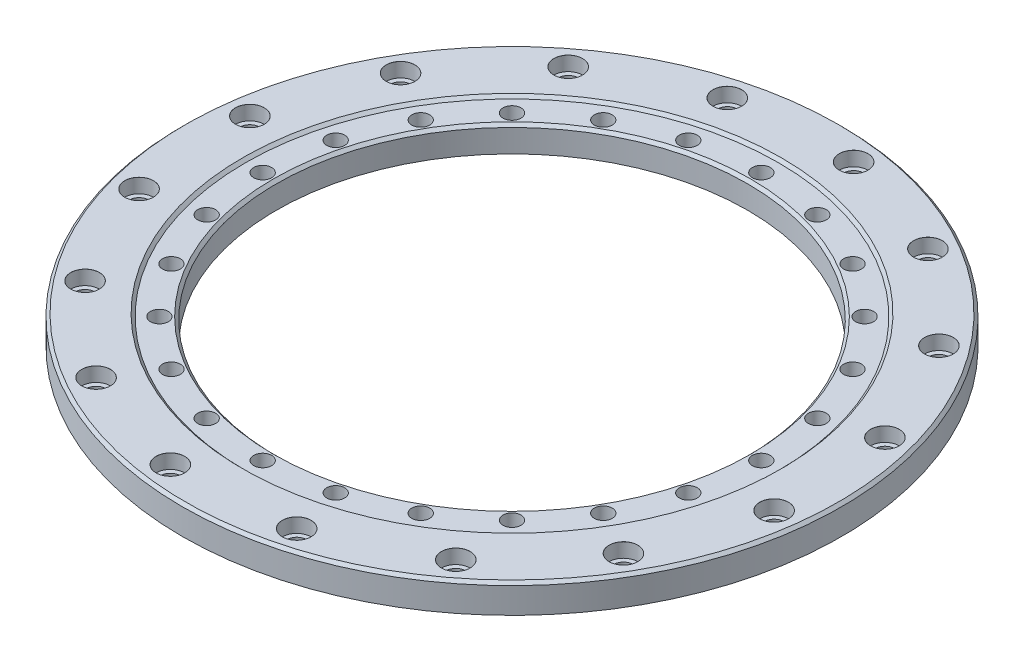
SolidWorks part; units mm, degrees
material "1.1191 (C45E)"
ref_plane "Front Plane" through (0, 0, 0) normal (0, 0, 1) x (1, 0, 0)
ref_plane "Top Plane" through (0, 0, 0) normal (0, 1, 0) x (1, 0, 0)
ref_plane "Right Plane" through (0, 0, 0) normal (1, 0, 0) x (0, 0, -1)
sketch "Sketch1" plane through (0, 0, 0) normal (1, 0, 0) x (0, 0, -1)
  line L0 (0, 0) -> (0, 173.9496) construction
  line L1 (-164.5, 0) -> (-230, 0)
  line L2 (-230, 0) -> (-230, 20)
  line L3 (-230, 20) -> (-186, 20)
  line L9 (-164.5, 18) -> (-164.5, 0)
  line L10 (-164.5, 18) -> (-186, 18)
  line L11 (-186, 18) -> (-186, 20)
  dimension "D1" = 460
  dimension "D2" = 372
  dimension "D3" = 329
  dimension "D4" = 20
  dimension "D5" = 18
revolve "Revolve1" add sketch "Sketch1" angle 360 about L0
sketch "Sketch2" plane through (0, 20, 0) normal (0, 1, 0) x (1, 0, 0)
  line L0 (0, 0) -> (0, 174) construction
  circle A0 centre (0, 0) radius 174 construction
  circle A1 centre (0, 174) radius 6.25
  circle A3 centre (45.0345, 168.0711) radius 6.25
  circle A4 centre (87, 150.6884) radius 6.25
  circle A5 centre (123.0366, 123.0366) radius 6.25
  circle A6 centre (150.6884, 87) radius 6.25
  circle A7 centre (168.0711, 45.0345) radius 6.25
  circle A8 centre (174, 0) radius 6.25
  circle A9 centre (168.0711, -45.0345) radius 6.25
  circle A10 centre (150.6884, -87) radius 6.25
  circle A11 centre (123.0366, -123.0366) radius 6.25
  circle A12 centre (87, -150.6884) radius 6.25
  circle A13 centre (45.0345, -168.0711) radius 6.25
  circle A14 centre (0, -174) radius 6.25
  circle A15 centre (-45.0345, -168.0711) radius 6.25
  circle A16 centre (-87, -150.6884) radius 6.25
  circle A17 centre (-123.0366, -123.0366) radius 6.25
  circle A18 centre (-150.6884, -87) radius 6.25
  circle A19 centre (-168.0711, -45.0345) radius 6.25
  circle A20 centre (-174, 0) radius 6.25
  circle A21 centre (-168.0711, 45.0345) radius 6.25
  circle A22 centre (-150.6884, 87) radius 6.25
  circle A23 centre (-123.0366, 123.0366) radius 6.25
  circle A24 centre (-87, 150.6884) radius 6.25
  circle A25 centre (-45.0345, 168.0711) radius 6.25
  point P55 (0, 0)
  dimension "D1" = 348
  dimension "D2" = 12.5
  dimension "D3" = 24
sketch "Sketch3" plane through (0, 20, 0) normal (0, 1, 0) x (1, 0, 0)
  line L0 (0, 0) -> (27.7368, 210.682) construction
  circle A0 centre (0, 0) radius 212.5 construction
  circle A1 centre (27.7368, 210.682) radius 5.5
  point P37 (0, 0)
  dimension "D1" = 7.5
  dimension "D2" = 425
  dimension "D3" = 11
extrude "Cut-Extrude3" cut sketch "Sketch2" against normal blind 20
hole_wizard "CBORE for M12 SHCS1" positions "Sketch6" profile "Sketch7" counterbore size "M12" standard "ANSI Metric" end condition through all
sketch "Sketch6" plane through (0, 20, 0) normal (0, 1, 0) x (1, 0, 0)
  point P0 (27.7368, 210.682)
sketch "Sketch7" plane through (27.7368, 20, -210.682) normal (1, 0, 0) x (0, 0, 1)
  line L0 (0, 0) -> (0, 20)
  line L1 (0, 20) -> (6.75, 20)
  line L3 (6.75, 20) -> (6.75, 10)
  line L4 (10, 10) -> (6.75, 10)
  line L5 (10, 10) -> (10, 0.025)
  line L6 (10, 0.025) -> (10.025, 0)
  line L7 (10.025, 0) -> (0, 0)
  line L8 (-10, 0.025) -> (-10.025, 0) construction
  line L11 (0, -6.35) -> (0, 107.95) construction
  dimension "Thru Hole Dia." = 13.5
  dimension "Thru Hole Depth" = 20
  dimension "C'Bore Dia." = 20
  dimension "C'Bore Depth" = 10
  dimension "Near C'Sink Dia." = 20.05
  dimension "Near C'Sink Angle" = 90
pattern_circular "CirPattern1" count 16 over 360 about axis through (0, 0, 0) along (0, -1, 0) of "CBORE for M12 SHCS1"
chamfer "Chamfer1" distance 2 angle 45 3 edges at (0, 20, -230) (0, 20, -186) (0, 18, -164.5)
sketch "Sketch8" plane through (0, 0, 0) normal (0, -1, 0) x (1, 0, 0)
  circle A0 centre (0, 0) radius 192
  dimension "D1" = 384
split line "Split Line1" [suppressed]
